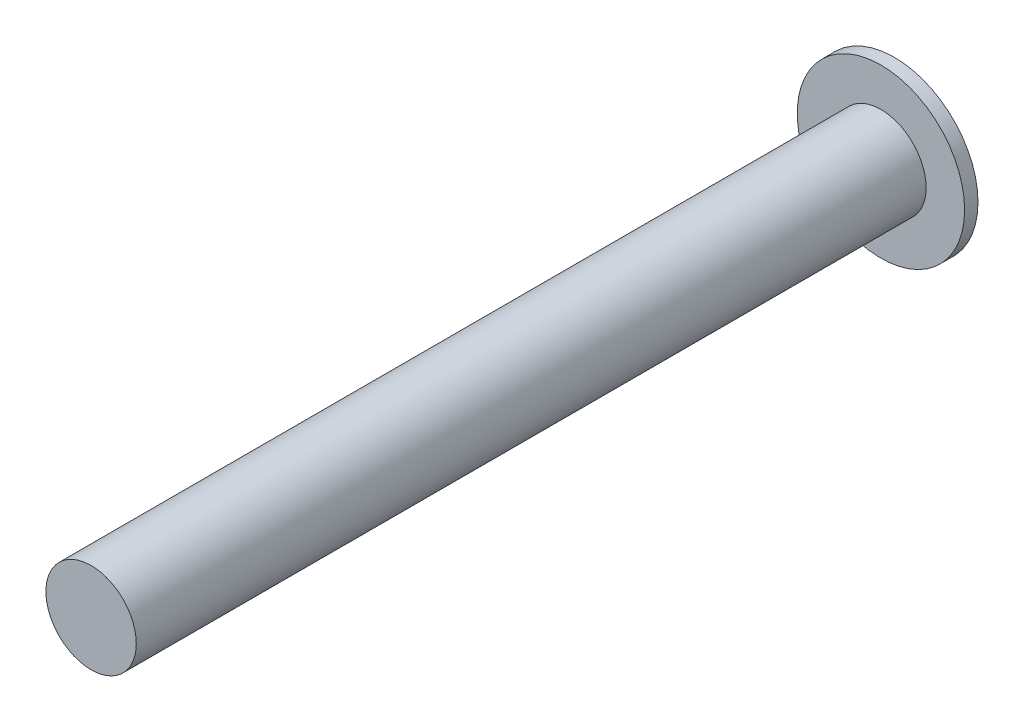
SolidWorks part; units mm, degrees
ref_plane "Front Plane" through (0, 0, 0) normal (0, 0, 1) x (1, 0, 0)
ref_plane "Top Plane" through (0, 0, 0) normal (0, 1, 0) x (1, 0, 0)
ref_plane "Right Plane" through (0, 0, 0) normal (1, 0, 0) x (0, 0, -1)
sketch "Sketch1" plane through (0, 0, 0) normal (0, 0, 1) x (1, 0, 0)
  circle A0 centre (0, 0) radius 12.5
  circle A1 centre (0, 0) radius 6.75
  circle A2 centre (0, 0) radius 5.75
  dimension "D1" = 25
  dimension "D2" = 13.5
  dimension "D3" = 11.5
extrude "Boss-Extrude1" add sketch "Sketch1" along normal blind 2 contours A0 A1 region at (-12.1464, 0, 0)
extrude "Boss-Extrude2" add sketch "Sketch1<3>" along normal blind 120 contours A2 | A1 A2 region at (-6.5591, 0, 0) region at (0, 0, 0)
sketch "Sketch1<3>" plane through (0, 0, 0) normal (0, 0, 1) x (1, 0, 0) same geometry as "Sketch1"
extrude "Cut-Extrude1" cut sketch "Sketch1<4>" along normal blind 115 contours A2 region at (0, 0, 0)
sketch "Sketch1<4>" plane through (0, 0, 0) normal (0, 0, 1) x (1, 0, 0) same geometry as "Sketch1"
ref_plane "Plane1" through (0, 0, 10) normal (0, 0, 1) x (1, 0, 0)
sketch "Sketch2" plane through (0, 0, 10) normal (0, 0, 1) x (1, 0, 0)
  line L5 (2.75, -9.5163) -> (-2.75, -9.5163)
  line L6 (2.75, -9.5163) -> (2.75, -3.9837)
  line L7 (2.75, -3.9837) -> (-2.75, -3.9837)
  line L8 (-2.75, -9.5163) -> (-2.75, -3.9837)
  line L9 (2.75, -9.5163) -> (-2.75, -3.9837) construction
  line L10 (2.75, -3.9837) -> (-2.75, -9.5163) construction
  circle A0 centre (0, 0) radius 6.75 construction
  circle A1 centre (0, 0) radius 6.75 construction
  point P0 (0, -6.75)
  point P1 (0, -6.75)
  dimension "D1" = 5.5
extrude "Cut-Extrude3" cut sketch "Sketch2" along normal blind 80
